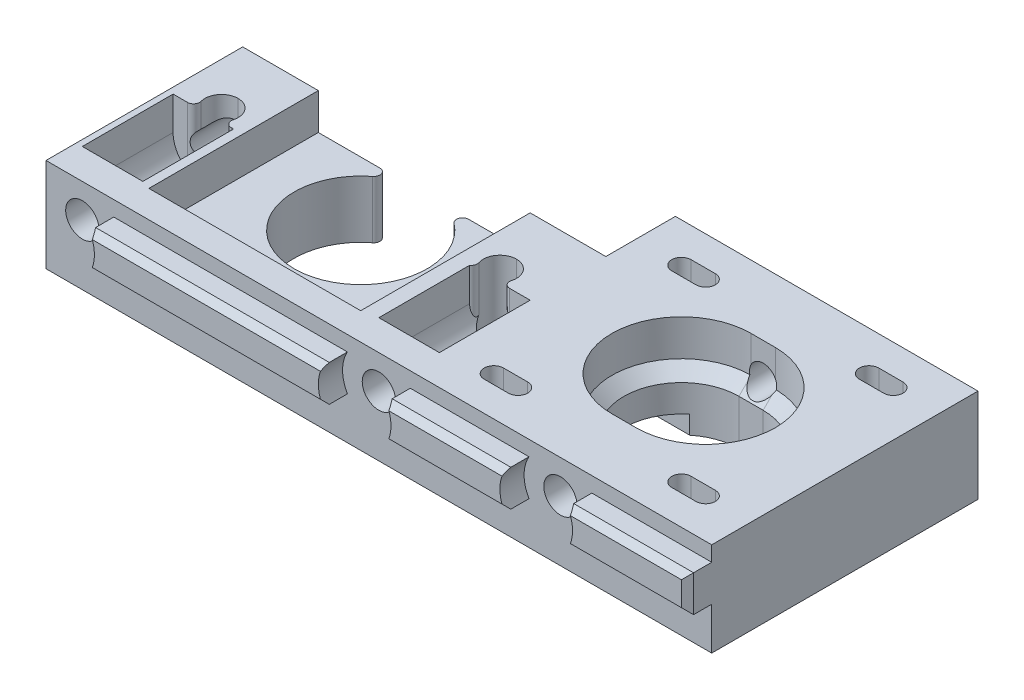
SolidWorks part; units mm, degrees
ref_plane "Front Plane" through (0, 0, 0) normal (0, 0, 1) x (1, 0, 0)
ref_plane "Top Plane" through (0, 0, 0) normal (0, 1, 0) x (1, 0, 0)
ref_plane "Right Plane" through (0, 0, 0) normal (1, 0, 0) x (0, 0, -1)
sketch "Sketch1" plane through (0, 0, 0) normal (0, 1, 0) x (1, 0, 0)
  line L0 (30, 0) -> (30, 7) construction
  line L1 (0, 0) -> (60, 0)
  line L2 (0, 0) -> (0, 32.5)
  line L3 (0, 32.5) -> (60, 32.5)
  line L4 (60, 0) -> (60, 32.5)
  line L5 (7, 7) -> (53, 7)
  line L6 (7, 7) -> (7, 22)
  line L7 (7, 22) -> (53, 22)
  line L8 (53, 7) -> (53, 22)
  dimension "D1" = 15
  dimension "D2" = 46
  dimension "D3" = 7
  dimension "D4" = 60
  dimension "D5" = 32.5
sketch "Sketch2" plane through (0, 0, 0) normal (0, 1, 0) x (1, 0, 0)
  line L1 (0, 32.5) -> (60, 32.5)
  line L2 (0, 32.5) -> (0, 0)
  line L3 (0, 0) -> (60, 0)
  line L4 (60, 32.5) -> (60, 0)
  circle A0 centre (7, 22) radius 2.75
  circle A1 centre (7, 7) radius 2.75 construction
  circle A2 centre (53, 7) radius 2.75 construction
  circle A3 centre (53, 22) radius 2.75
  dimension "D1" = 5.5
extrude "Boss-Extrude1" add sketch "Sketch2" along normal blind 15.5
sketch "Sketch3" plane through (0, 15.5, 0) normal (0, 1, 0) x (1, 0, 0)
  line L0 (30, 22) -> (30, 0) construction
  line L1 (12.5, 4.5) -> (47.5, 4.5)
  line L2 (12.5, 4.5) -> (12.5, 39.5)
  line L3 (12.5, 39.5) -> (47.5, 39.5)
  line L4 (47.5, 4.5) -> (47.5, 39.5)
  line L5 (12.5, 4.5) -> (47.5, 39.5) construction
  line L6 (12.5, 39.5) -> (47.5, 4.5) construction
  line L7 (0, 0) -> (60, 0) construction
  point P0 (30, 22)
  dimension "D1" = 35
  dimension "D2" = 4.5
extrude "Cut-Extrude1" cut sketch "Sketch3" against normal blind 6
sketch "Sketch4" plane through (0, 9.5, 0) normal (0, 1, 0) x (1, 0, 0)
  line L0 (7, 22) -> (53, 22) construction
  circle A0 centre (30, 22) radius 11
  point P4 (0, 0)
  dimension "D1" = 22
extrude "Cut-Extrude2" cut sketch "Sketch4" against normal through all
fillet "Fillet1" radius 1 2 edges at (26.7213, 4.75, -32.5) (33.2787, 4.75, -32.5)
sketch "Sketch6" plane through (0, 0, 0) normal (0, -1, 0) x (1, 0, 0)
  line L0 (84.9994, -15.6336) -> (30, -15.6336)
  line L1 (84.9994, -28.3664) -> (30, -28.3664)
  line L3 (63.8494, -43.15) -> (106.1494, -43.15)
  line L4 (63.8494, -43.15) -> (63.8494, -0.85)
  line L5 (63.8494, -0.85) -> (106.1494, -0.85)
  line L6 (106.1494, -43.15) -> (106.1494, -0.85)
  line L7 (63.8494, -43.15) -> (106.1494, -0.85) construction
  line L8 (63.8494, -0.85) -> (106.1494, -43.15) construction
  line L9 (69.4994, -37.5) -> (100.4994, -37.5)
  line L10 (69.4994, -37.5) -> (69.4994, -6.5)
  line L11 (69.4994, -6.5) -> (100.4994, -6.5)
  line L12 (100.4994, -37.5) -> (100.4994, -6.5)
  line L13 (69.4994, -37.5) -> (100.4994, -6.5) construction
  line L14 (69.4994, -6.5) -> (100.4994, -37.5) construction
  arc A0 (30, -28.3664) -> (30, -15.6336) centre (30, -22) cw
  arc A1 (84.9994, -15.6336) -> (84.9994, -28.3664) centre (84.9994, -22) cw
  point P7 (0, 0)
  point P8 (0, 0)
  point P17 (0, 0)
  point P18 (0, 0)
  point P19 (0, 0)
  dimension "D1" = 6.3664
  dimension "D2" = 150
  dimension "D3" = 42.3
  dimension "D4" = 31
ref_plane "Plane1" through (0, 12, 0) normal (0, -1, 0) x (-1, 0, 0)
sketch "Sketch8" plane through (0, 0, 0) normal (0, -1, 0) x (1, 0, 0)
  line L0 (60, -22) -> (63.8494, -22) construction
  line L1 (60, 0) -> (109.9988, 0)
  line L2 (60, 0) -> (60, -44)
  line L3 (60, -44) -> (109.9988, -44)
  line L4 (109.9988, 0) -> (109.9988, -44)
  line L5 (63.8494, -43.15) -> (63.8494, -0.85) construction
  line L6 (106.1494, -22) -> (109.9988, -22) construction
  line L7 (106.1494, -43.15) -> (106.1494, -0.85) construction
  point P9 (106.1537, -24.129)
extrude "Boss-Extrude3" add sketch "Sketch8" against normal up to surface (15.5 mm away) up to face at (30, 15.5, -17.375)
sketch "Sketch9" plane through (0, 15.5, 0) normal (0, 1, 0) x (1, 0, 0)
  line L0 (82.9994, 22) -> (86.9994, 22) construction
  line L1 (67.4994, 6.5) -> (71.4994, 6.5) construction
  line L2 (98.4994, 6.5) -> (102.4994, 6.5) construction
  line L3 (67.4994, 37.5) -> (71.4994, 37.5) construction
  line L4 (98.4994, 37.5) -> (102.4994, 37.5) construction
  line L5 (82.9994, 10.5) -> (86.9994, 10.5)
  line L6 (82.9994, 33.5) -> (86.9994, 33.5)
  line L7 (67.4994, 4.9) -> (71.4994, 4.9)
  line L8 (67.4994, 35.9) -> (71.4994, 35.9)
  line L9 (98.4994, 35.9) -> (102.4994, 35.9)
  line L10 (98.4994, 4.9) -> (102.4994, 4.9)
  line L11 (67.4994, 8.1) -> (71.4994, 8.1)
  line L12 (67.4994, 39.1) -> (71.4994, 39.1)
  line L13 (98.4994, 39.1) -> (102.4994, 39.1)
  line L14 (98.4994, 8.1) -> (102.4994, 8.1)
  arc A0 (82.9994, 10.5) -> (82.9994, 33.5) centre (82.9994, 22) cw
  arc A1 (86.9994, 10.5) -> (86.9994, 33.5) centre (86.9994, 22) ccw
  arc A2 (67.4994, 4.9) -> (67.4994, 8.1) centre (67.4994, 6.5) cw
  arc A3 (71.4994, 4.9) -> (71.4994, 8.1) centre (71.4994, 6.5) ccw
  arc A4 (67.4994, 35.9) -> (67.4994, 39.1) centre (67.4994, 37.5) cw
  arc A5 (71.4994, 35.9) -> (71.4994, 39.1) centre (71.4994, 37.5) ccw
  arc A6 (98.4994, 35.9) -> (98.4994, 39.1) centre (98.4994, 37.5) cw
  arc A7 (102.4994, 35.9) -> (102.4994, 39.1) centre (102.4994, 37.5) ccw
  arc A8 (98.4994, 4.9) -> (98.4994, 8.1) centre (98.4994, 6.5) cw
  arc A9 (102.4994, 4.9) -> (102.4994, 8.1) centre (102.4994, 6.5) ccw
  point P0 (100.4994, 6.5)
  point P3 (84.9994, 22)
  point P4 (100.4994, 37.5)
  point P8 (69.4994, 37.5)
  point P10 (69.4994, 6.5)
  point P15 (69.4994, 6.5)
  point P18 (100.4994, 6.5)
  point P21 (69.4994, 37.5)
  point P24 (100.4994, 37.5)
  dimension "D1" = 4
  dimension "D2" = 11.5
  dimension "D3" = 11.5
  dimension "D4" = 1.6
  dimension "D5" = 1.6
extrude "Cut-Extrude3" cut sketch "Sketch9" against normal blind 6
sketch "Sketch10" plane through (0, 9.5, 0) normal (0, 1, 0) x (1, 0, 0)
  line L4 (82.9994, 12.5) -> (86.9994, 12.5)
  line L5 (86.9994, 31.5) -> (82.9994, 31.5)
  line L6 (82.9994, 12.5) -> (86.9994, 12.5)
  line L7 (86.9994, 31.5) -> (82.9994, 31.5)
  line L10 (67.4994, 2.9) -> (71.4994, 2.9)
  line L11 (71.4994, 10.1) -> (67.4994, 10.1)
  line L12 (67.4994, 2.9) -> (71.4994, 2.9)
  line L13 (71.4994, 10.1) -> (67.4994, 10.1)
  line L16 (98.4994, 2.9) -> (102.4994, 2.9)
  line L17 (102.4994, 10.1) -> (98.4994, 10.1)
  line L18 (98.4994, 2.9) -> (102.4994, 2.9)
  line L19 (102.4994, 10.1) -> (98.4994, 10.1)
  line L22 (98.4994, 33.9) -> (102.4994, 33.9)
  line L23 (102.4994, 41.1) -> (98.4994, 41.1)
  line L24 (98.4994, 33.9) -> (102.4994, 33.9)
  line L25 (102.4994, 41.1) -> (98.4994, 41.1)
  line L28 (67.4994, 33.9) -> (71.4994, 33.9)
  line L29 (71.4994, 41.1) -> (67.4994, 41.1)
  line L30 (67.4994, 33.9) -> (71.4994, 33.9)
  line L31 (71.4994, 41.1) -> (67.4994, 41.1)
  arc A4 (82.9994, 31.5) -> (82.9994, 12.5) centre (82.9994, 22) ccw
  arc A5 (86.9994, 12.5) -> (86.9994, 31.5) centre (86.9994, 22) ccw
  arc A6 (82.9994, 31.5) -> (82.9994, 12.5) centre (82.9994, 22) ccw
  arc A7 (86.9994, 12.5) -> (86.9994, 31.5) centre (86.9994, 22) ccw
  arc A10 (67.4994, 10.1) -> (67.4994, 2.9) centre (67.4994, 6.5) ccw
  arc A11 (71.4994, 2.9) -> (71.4994, 10.1) centre (71.4994, 6.5) ccw
  arc A12 (67.4994, 10.1) -> (67.4994, 2.9) centre (67.4994, 6.5) ccw
  arc A13 (71.4994, 2.9) -> (71.4994, 10.1) centre (71.4994, 6.5) ccw
  arc A16 (98.4994, 10.1) -> (98.4994, 2.9) centre (98.4994, 6.5) ccw
  arc A17 (102.4994, 2.9) -> (102.4994, 10.1) centre (102.4994, 6.5) ccw
  arc A18 (98.4994, 10.1) -> (98.4994, 2.9) centre (98.4994, 6.5) ccw
  arc A19 (102.4994, 2.9) -> (102.4994, 10.1) centre (102.4994, 6.5) ccw
  arc A22 (98.4994, 41.1) -> (98.4994, 33.9) centre (98.4994, 37.5) ccw
  arc A23 (102.4994, 33.9) -> (102.4994, 41.1) centre (102.4994, 37.5) ccw
  arc A24 (98.4994, 41.1) -> (98.4994, 33.9) centre (98.4994, 37.5) ccw
  arc A25 (102.4994, 33.9) -> (102.4994, 41.1) centre (102.4994, 37.5) ccw
  arc A28 (67.4994, 41.1) -> (67.4994, 33.9) centre (67.4994, 37.5) ccw
  arc A29 (71.4994, 33.9) -> (71.4994, 41.1) centre (71.4994, 37.5) ccw
  arc A30 (67.4994, 41.1) -> (67.4994, 33.9) centre (67.4994, 37.5) ccw
  arc A31 (71.4994, 33.9) -> (71.4994, 41.1) centre (71.4994, 37.5) ccw
  dimension "D1" = 2
  dimension "D2" = 2
  dimension "D3" = 2
  dimension "D4" = 2
  dimension "D5" = 2
extrude "Cut-Extrude4" cut sketch "Sketch10" against normal through all
sketch "Sketch5" plane through (0, 0, 0) normal (0, 0, 1) x (1, 0, 0)
  line L0 (0, 15.5) -> (0, 0) construction
  line L1 (0, 13) -> (109.9988, 13)
  line L2 (0, 13) -> (0, 7)
  line L3 (0, 7) -> (109.9988, 7)
  line L4 (109.9988, 13) -> (109.9988, 7)
  line L6 (0, 0) -> (109.9988, 0) construction
  line L9 (109.9988, 15.5) -> (109.9988, 0) construction
  point P6 (0, 0)
  dimension "D1" = 7
  dimension "D2" = 6
extrude "Boss-Extrude2" add sketch "Sketch5" along normal blind 4
chamfer "Chamfer1" distance 1 angle 45 4 edges at (54.9994, 13, 4) (109.9988, 10, 4) (54.9994, 7, 4) (0, 10, 4)
ref_plane "Plane2" through (0, 0, -20) normal (0, 0, 1) x (1, 0, 0)
sketch "Sketch12" plane through (0, 0, -20) normal (0, 0, -1) x (-1, 0, 0)
  line L0 (-109.9988, 10) -> (0, 10) construction
  line L1 (-109.9988, 15.5) -> (-109.9988, 0) construction
  line L2 (0, 15.5) -> (0, 0) construction
  line L3 (-60, 0) -> (-109.9988, 0) construction
  line L4 (-60, 15.5) -> (-60, 0) construction
  line L5 (-84.9994, 15.5) -> (-84.9994, 10) construction
  line L6 (-60, 15.5) -> (-109.9988, 15.5) construction
  point P6 (-6, 10)
  point P9 (-55, 10)
  point P16 (0, 0)
  dimension "D1" = 10
  dimension "D2" = 6
  dimension "D3" = 5
hole_wizard "CBORE for M5 SHCS3" positions "Sketch13" profile "Sketch14" counterbore size "M5" standard "ANSI Metric" end condition through all
sketch "Sketch13" plane through (0, 0, -20) normal (0, 0, -1) x (-1, 0, 0)
  point P0 (-55, 10)
  point P3 (-6, 10)
  point P9 (-84.9994, 10)
sketch "Sketch14" plane through (55, 10, -20) normal (1, 0, 0) x (0, 1, 0)
  line L0 (0, 0) -> (0, 24)
  line L1 (0, 24) -> (2.75, 24)
  line L3 (2.75, 24) -> (2.75, 15)
  line L4 (2.75, 15) -> (5, 15)
  line L5 (5, 15) -> (5, 0)
  line L7 (5, 0) -> (0, 0)
  line L11 (0, -6.35) -> (0, 107.95) construction
  dimension "Thru Hole Dia." = 5.5
  dimension "Thru Hole Depth" = 24
  dimension "C'Bore Dia." = 10
  dimension "C'Bore Depth" = 15
sketch "Sketch11" plane through (0, 0, 0) normal (0, -1, 0) x (1, 0, 0)
  line L1 (57.7343, -22) -> (55.3671, -17.9)
  line L2 (55.3671, -17.9) -> (50.6329, -17.9)
  line L3 (50.6329, -17.9) -> (48.2657, -22)
  line L4 (48.2657, -22) -> (50.6329, -26.1)
  line L5 (50.6329, -26.1) -> (55.3671, -26.1)
  line L6 (55.3671, -26.1) -> (57.7343, -22)
  line L7 (11.7343, -22) -> (9.3671, -17.9)
  line L8 (9.3671, -17.9) -> (4.6329, -17.9)
  line L9 (4.6329, -17.9) -> (2.2657, -22)
  line L10 (2.2657, -22) -> (4.6329, -26.1)
  line L11 (4.6329, -26.1) -> (9.3671, -26.1)
  line L12 (9.3671, -26.1) -> (11.7343, -22)
  circle A0 centre (53, -22) radius 4.1 construction
  circle A1 centre (7, -22) radius 4.1 construction
  dimension "D1" = 8.2
extrude "Cut-Extrude5" cut sketch "Sketch11" against normal blind 4.5
sketch "Sketch15" plane through (0, 0, 4) normal (0, 0, 1) x (1, 0, 0)
  line L0 (0.8038, 7) -> (0, 7)
  line L1 (0, 7) -> (0, 13)
  line L2 (0, 13) -> (0.8038, 13)
  line L3 (0, 13) -> (109.9988, 13) construction
  line L4 (0, 7) -> (109.9988, 7) construction
  line L6 (0, 7) -> (0, 13) construction
  arc A0 (0.8038, 7) -> (0.8038, 13) centre (6, 10) ccw
  circle A1 centre (55, 10) radius 6
  circle A2 centre (84.9994, 10) radius 6
  arc A3 (86.8869, 8) -> (86.8869, 12) centre (84.9994, 10) ccw construction
  arc A4 (4.1125, 12) -> (4.1125, 8) centre (6, 10) ccw construction
  dimension "D1" = 12
extrude "Cut-Extrude6" cut sketch "Sketch15" against normal up to surface (4 mm away) up to face at (54.9994, 14.25, 0)
sketch "Sketch16" plane through (0, 0, 0) normal (0, -1, 0) x (1, 0, 0)
  line L4 (30, -29.3664) -> (84.9994, -29.3664)
  line L5 (84.9994, -14.6336) -> (30, -14.6336)
  line L6 (30, -29.3664) -> (84.9994, -29.3664)
  line L7 (84.9994, -14.6336) -> (30, -14.6336)
  arc A4 (84.9994, -29.3664) -> (84.9994, -14.6336) centre (84.9994, -22) ccw
  arc A5 (30, -14.6336) -> (30, -29.3664) centre (30, -22) ccw
  arc A6 (84.9994, -29.3664) -> (84.9994, -14.6336) centre (84.9994, -22) ccw
  arc A7 (30, -14.6336) -> (30, -29.3664) centre (30, -22) ccw
  dimension "D1" = 1
extrude "Cut-Extrude7" cut sketch "Sketch16" against normal blind 3
chamfer "Chamfer2" distance 2 angle 45 3 edges at (73.6196, 9.5, -23.5065) (96.3792, 9.5, -23.5065) (84.9994, 9.5, -31.5)
sketch "Sketch17" plane through (0, 15.5, 0) normal (0, 1, 0) x (1, 0, 0)
  line L1 (60, 5) -> (50, 5) construction
  line L3 (60, 5) -> (50, 5)
  line L4 (11, 5) -> (1, 5) construction
  line L9 (11, 5) -> (1, 5)
  line L10 (50, 5) -> (50, 20)
  line L11 (50, 20) -> (60, 20)
  line L12 (60, 20) -> (60, 5)
  line L13 (11, 5) -> (11, 20)
  line L14 (11, 20) -> (1, 20)
  line L15 (1, 20) -> (1, 5)
  line L16 (54.8875, 20) -> (60, 20) construction
  point P7 (60, 17.2048)
extrude "Cut-Extrude8" cut sketch "Sketch17" against normal up to next
fillet "Fillet2" radius 1 4 edges at (5.1125, 10.2897, -20) (8.8875, 10.709, -20) (51.1125, 11.1778, -20) (54.8875, 10.2506, -20)
sketch "Sketch18" plane through (0, 0, -32.5) normal (0, 0, -1) x (-1, 0, 0)
  circle A0 centre (-6, 10) radius 2.25
  circle A1 centre (-55, 10) radius 2.25
  circle A2 centre (-84.9994, 10) radius 2.25
  circle A3 centre (-55, 10) radius 2.75 construction
  circle A4 centre (-6, 10) radius 2.75 construction
  dimension "D1" = 4.5
extrude "Cut-Extrude9" cut sketch "Sketch18" against normal through all and the other way through all
